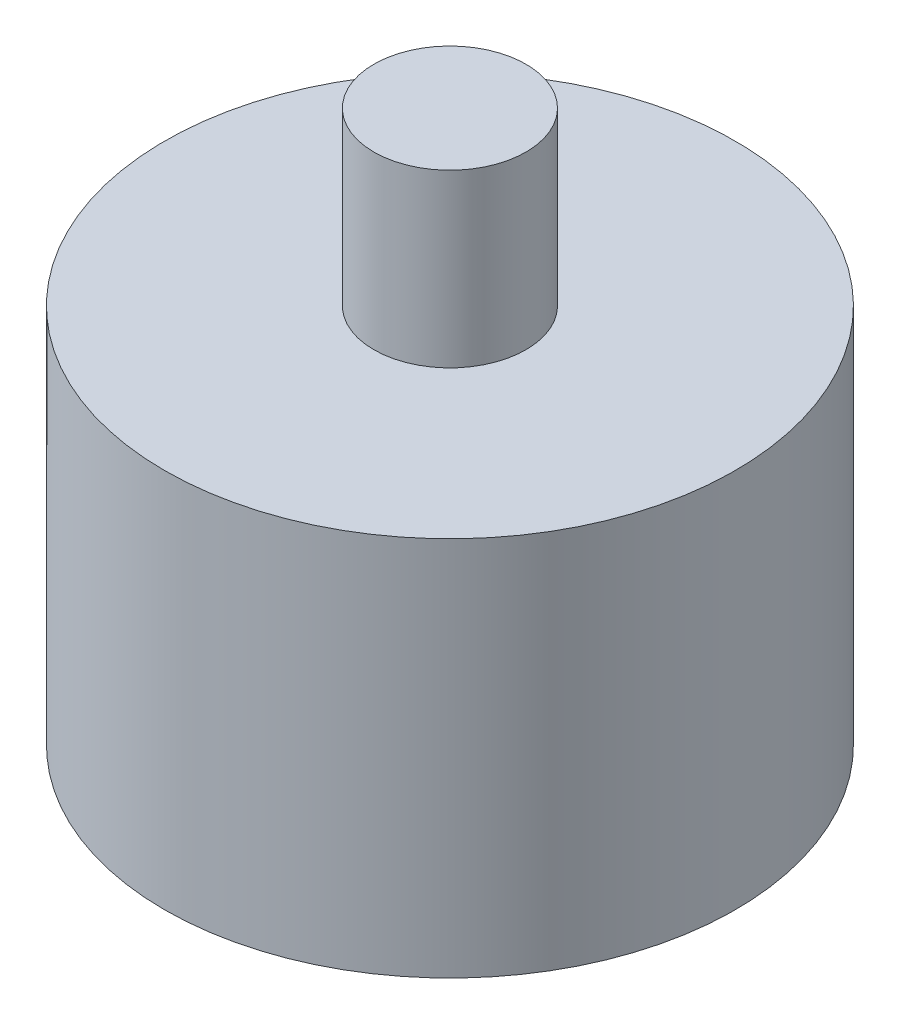
SolidWorks part; units mm, degrees
ref_plane "Front Plane" through (0, 0, 0) normal (0, 0, 1) x (1, 0, 0)
ref_plane "Top Plane" through (0, 0, 0) normal (0, 1, 0) x (1, 0, 0)
ref_plane "Right Plane" through (0, 0, 0) normal (1, 0, 0) x (0, 0, -1)
sketch "Sketch1" plane through (0, 0, 0) normal (0, 1, 0) x (1, 0, 0)
  circle A0 centre (0, 0) radius 15
extrude "Boss-Extrude1" add sketch "Sketch1" along normal blind 20
sketch "Sketch2" plane through (0, 20, 0) normal (0, 1, 0) x (1, 0, 0)
  circle A0 centre (0, 0) radius 4
extrude "Boss-Extrude2" add sketch "Sketch2" along normal blind 9
